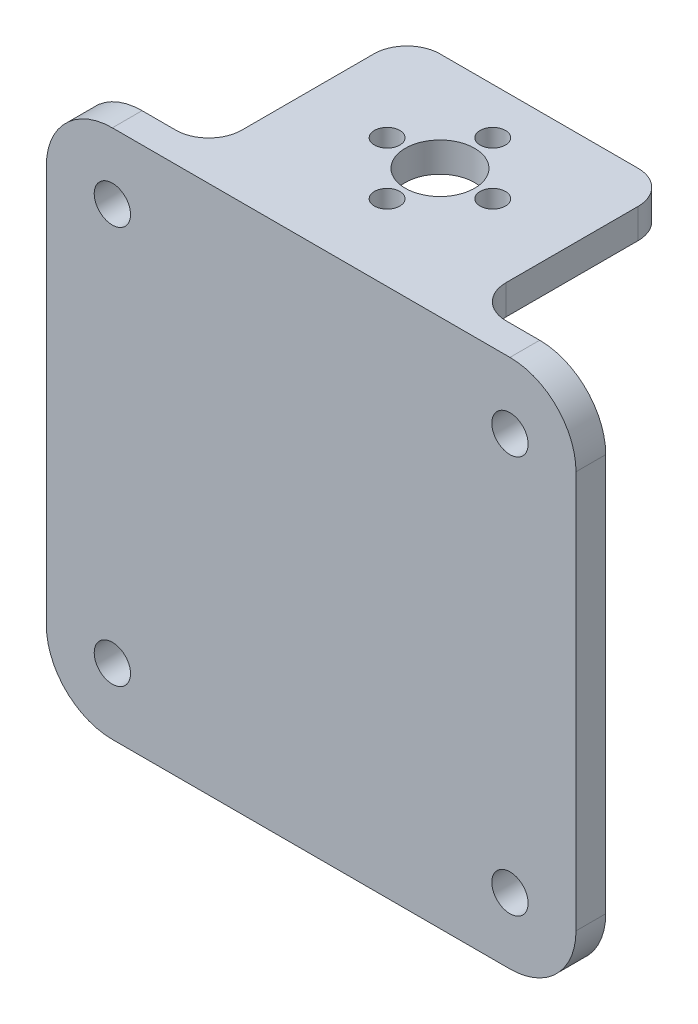
SolidWorks part; units mm, degrees
ref_plane "Front Plane" through (0, 0, 0) normal (0, 0, 1) x (1, 0, 0)
ref_plane "Top Plane" through (0, 0, 0) normal (0, 1, 0) x (1, 0, 0)
ref_plane "Right Plane" through (0, 0, 0) normal (1, 0, 0) x (0, 0, -1)
sketch "Sketch1" plane through (0, 0, 0) normal (0, 0, 1) x (1, 0, 0)
  line L0 (-30.1, 0) -> (30.1, 0) construction
  line L1 (-40.1, -40.1) -> (40.1, -40.1)
  line L2 (-40.1, -40.1) -> (-40.1, 40.1)
  line L3 (-40.1, 40.1) -> (40.1, 40.1)
  line L4 (40.1, -40.1) -> (40.1, 40.1)
  line L5 (-40.1, -40.1) -> (40.1, 40.1) construction
  line L6 (-40.1, 40.1) -> (40.1, -40.1) construction
  line L7 (55, 0) -> (-55, 0) construction
  line L8 (-30.1, -30.1) -> (-30.1, 30.1) construction
  line L9 (30.1, -30.1) -> (30.1, 30.1) construction
  point P0 (0, 0)
  point P11 (0, 0)
  point P14 (-30.1, 0)
  point P17 (30.1, 0)
  dimension "D1" = 60.2
  dimension "D2" = 60.2
  dimension "D3" = 10
  dimension "D4" = 10
extrude "Boss-Extrude1" add sketch "Sketch1" along normal blind 4.5
hole_wizard "M5 Clearance Hole1" positions "3DSketch1" profile "Sketch2" hole size "M5" standard "ANSI Metric" end condition through all
sketch3d "3DSketch1"
  line L0 (-40.1, -40.1, 0) -> (40.1, 40.1, 0) construction
  point P0 (30.1, 30.1, 0)
  point P3 (-30.1, 30.1, 0)
  point P6 (-30.1, -30.1, 0)
  point P10 (30.1, -30.1, 0)
  point P14 (30.1, 30.1, 0)
  point P16 (-30.1, 30.1, 0)
  point P18 (30.1, -30.1, 0)
  point P20 (-30.1, -30.1, 0)
sketch "Sketch2" plane through (-30.1, -30.1, 0) normal (1, 0, 0) x (0, 1, 0)
  line L0 (0, 0) -> (0, 4.5)
  line L1 (0, 4.5) -> (2.75, 4.5)
  line L2 (2.75, 4.5) -> (2.75, 0)
  line L5 (2.75, 0) -> (0, 0)
  line L11 (0, -6.35) -> (0, 107.95) construction
  dimension "Thru Hole Dia." = 5.5
  dimension "Thru Hole Depth" = 4.5
sketch "Sketch3" plane through (0, 0, 0) normal (0, 0, -1) x (-1, 0, 0)
  line L0 (-40.1, 40.1) -> (40.1, 40.1) construction
  line L1 (20, 40.1) -> (-20, 40.1)
  line L2 (20, 40.1) -> (20, 35.6)
  line L3 (20, 35.6) -> (-20, 35.6)
  line L4 (-20, 40.1) -> (-20, 35.6)
  line L5 (0, 2.475) -> (0, -2.475) construction
  point P6 (0, 40.1)
  dimension "D1" = 40
  dimension "D2" = 4.5
extrude "Boss-Extrude2" add sketch "Sketch3" along normal blind 30
sketch "Sketch4" plane through (0, 35.6, 0) normal (0, -1, 0) x (-1, 0, 0)
  line L0 (0, 0) -> (0, 15) construction
  line L1 (-20, 0) -> (20, 0) construction
  circle A0 centre (0, 15) radius 5.25
  dimension "D2" = 10.5
  dimension "D1" = 15
extrude "Cut-Extrude1" cut sketch "Sketch4" against normal up to next
sketch "Sketch5" plane through (0, 35.6, 0) normal (0, -1, 0) x (1, 0, 0)
  line L0 (0, -7) -> (0, -23) construction
  line L1 (8, -15) -> (-8, -15) construction
  circle A0 centre (0, -23) radius 1.9245
  circle A1 centre (-8, -15) radius 1.9245
  circle A2 centre (0, -7) radius 1.9245
  circle A3 centre (8, -15) radius 1.9245
  point P5 (0, -15)
  point P8 (0, -15)
  dimension "D1" = 16
extrude "Cut-Extrude2" cut sketch "Sketch5" against normal up to next
fillet "Fillet2" radius 10 4 edges at (40.1, -40.1, 2.25) (-40.1, -40.1, 2.25) (-40.1, 40.1, 2.25) (40.1, 40.1, 2.25)
fillet "Fillet4" radius 5 1 edges at (0, 35.6, 0)
fillet "Fillet3" radius 5 2 edges at (-20, 37.85, -30) (20, 37.85, -30)
sketch "Sketch6" plane through (0, 35.6, 0) normal (0, -1, 0) x (1, 0, 0)
  circle A0 centre (0, -15) radius 11.25
  dimension "D1" = 22.5
extrude "Cut-Extrude3" cut sketch "Sketch6" along normal up to next contours A0
fillet "Fillet5" radius 5 2 edges at (-20, 35.35, 0) (20, 35.35, 0)
